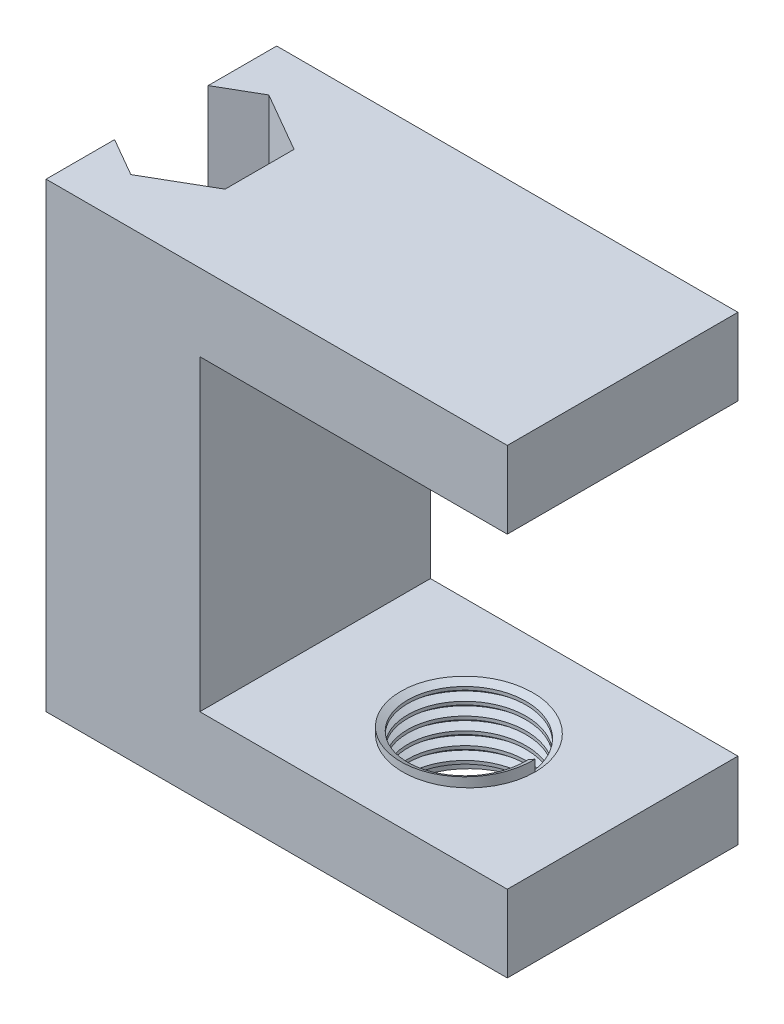
SolidWorks part; units mm, degrees
ref_plane "Front Plane" through (0, 0, 0) normal (0, 0, 1) x (1, 0, 0)
ref_plane "Top Plane" through (0, 0, 0) normal (0, 1, 0) x (1, 0, 0)
ref_plane "Right Plane" through (0, 0, 0) normal (1, 0, 0) x (0, 0, -1)
sketch "Sketch1" plane through (0, 0, 0) normal (0, 0, 1) x (1, 0, 0)
  line L1 (-19.05, -19.05) -> (19.05, -19.05)
  line L2 (-19.05, -19.05) -> (-19.05, 19.05)
  line L3 (-19.05, 19.05) -> (19.05, 19.05)
  line L4 (19.05, -19.05) -> (19.05, 19.05)
  line L5 (-19.05, -19.05) -> (19.05, 19.05) construction
  line L6 (-19.05, 19.05) -> (19.05, -19.05) construction
  point P0 (0, 0)
  dimension "D1" = 38.1
  dimension "D2" = 38.1
extrude "Boss-Extrude1" add sketch "Sketch1" against normal blind 19.05
sketch "Sketch2" plane through (0, 0, 0) normal (0, 0, 1) x (1, 0, 0)
  line L0 (19.05, 12.7) -> (-6.35, 12.7)
  line L1 (19.05, -19.05) -> (19.05, 19.05) construction
  line L2 (-6.35, 12.7) -> (-6.35, -12.7)
  line L3 (-6.35, -12.7) -> (19.05, -12.7)
  line L4 (19.05, -12.7) -> (19.05, 12.7)
  line L5 (19.05, 19.05) -> (-19.05, 19.05) construction
  line L6 (-19.05, -19.05) -> (19.05, -19.05) construction
  line L7 (-19.05, 19.05) -> (-19.05, -19.05) construction
  dimension "D1" = 6.35
  dimension "D2" = 6.35
  dimension "D3" = 12.7
extrude "Cut-Extrude1" cut sketch "Sketch2" against normal up to next
sketch "Sketch3" plane through (0, 19.05, 0) normal (0, 1, 0) x (1, 0, 0)
  line L0 (-19.05, 9.525) -> (19.05, 9.525) construction
  line L1 (-19.05, 19.05) -> (-19.05, 0) construction
  line L2 (19.05, 19.05) -> (19.05, 0) construction
  line L4 (-12.7, 11.3581) -> (-15.875, 13.1912)
  line L5 (-15.875, 13.1912) -> (-19.05, 11.3581)
  line L6 (-19.05, 11.3581) -> (-19.05, 7.6919)
  line L7 (-19.05, 7.6919) -> (-15.875, 5.8588)
  line L8 (-15.875, 5.8588) -> (-12.7, 7.6919)
  line L9 (-12.7, 7.6919) -> (-12.7, 11.3581)
  circle A0 centre (-15.875, 9.525) radius 3.175 construction
  dimension "D1" = 6.35
extrude "Cut-Extrude2" cut sketch "Sketch3" against normal up to next
sketch "Sketch4" plane through (0, 19.05, 0) normal (0, 1, 0) x (1, 0, 0)
  line L0 (19.05, 9.525) -> (-19.05, 9.525) construction
  line L1 (19.05, 19.05) -> (19.05, 0) construction
  line L2 (-15.875, 13.7201) -> (-15.875, 24.6297) construction
  line L3 (-19.05, 7.6919) -> (-6.001, 15.2258) construction
  line L4 (-19.05, 11.3581) -> (-13.6473, 8.2388) construction
  line L5 (-19.05, 13.3901) -> (-15.875, 15.2232)
  line L6 (-19.05, 19.05) -> (-19.05, 11.3581) construction
  line L7 (-15.875, 15.2232) -> (-10.9402, 12.3741)
  line L8 (-10.9402, 12.3741) -> (-10.9402, 6.6759)
  line L9 (-10.9402, 6.6759) -> (-15.875, 3.8268)
  line L10 (-15.875, 3.8268) -> (-19.05, 5.6599)
  line L11 (-19.05, 7.6919) -> (-19.05, 0) construction
  line L12 (-19.05, 5.6599) -> (-19.05, 7.6919)
  line L13 (-19.05, 13.3901) -> (-19.05, 11.3581)
  line L14 (-19.05, 11.3581) -> (-15.875, 13.1912)
  line L15 (-15.875, 13.1912) -> (-12.7, 11.3581)
  line L16 (-12.7, 11.3581) -> (-12.7, 7.6919)
  line L17 (-12.7, 7.6919) -> (-15.875, 5.8588)
  line L18 (-15.875, 5.8588) -> (-19.05, 7.6919)
  dimension "D1" = 2.032
  dimension "D2" = 2.032
  dimension "D3" = 2.032
  dimension "D4" = 2.032
  dimension "D5" = 2.032
extrude "Cut-Extrude3" cut sketch "Sketch4" against normal blind 31.75
sketch "Sketch5" plane through (0, -19.05, 0) normal (0, -1, 0) x (1, 0, 0)
  line L0 (19.05, -9.525) -> (-19.3242, -9.525) construction
  line L1 (19.05, -19.05) -> (19.05, 0) construction
  line L2 (19.05, 0) -> (-6.35, 0) construction
  line L3 (-19.05, 0) -> (19.05, 0) construction
  line L4 (-6.35, 0) -> (-6.35, -9.525) construction
  line L5 (6.35, 0) -> (6.35, -9.525) construction
  circle A0 centre (6.35, -9.525) radius 5.461
  dimension "D2" = 10.922
  dimension "D1" = 25.4
extrude "Cut-Extrude4" cut sketch "Sketch5" against normal up to next
thread "Thread1" pitch 1.0583 method extrude profile "Thread Profile1" start angle 0, offset 0, length 0, pitch 1.0583, diameter 10.922
ref_plane "Plane1" through (11.811, -19.05, -9.525) normal (0, 0, 1) x (1, 0, 0)
sketch "Thread Profile1" plane through (11.811, -19.05, -9.525) normal (0, 0, 1) x (1, 0, 0)
  line L0 (0, 0) -> (0, 1.0583) construction
  line L11 (0, 0) -> (0, 0.926)
  line L12 (0, 0.926) -> (-0.5728, 0.5953)
  line L13 (-0.5728, 0.5953) -> (-0.5728, 0.3307)
  line L15 (-0.5728, 0.3307) -> (0, 0)
  line L17 (-0.5728, 0.463) -> (0, 0.463) construction
  point P2 (0, 0)
  dimension "Pitch" = 1.0583
  dimension "Profile_Angle" = 60
  dimension "Profile_Land" = 0.2646
  dimension "Profile_Height" = 0.5728
equation "\"G\"= 0.08"
equation "\"D1@Sketch4\"=\"G\""
equation "\"D2@Sketch4\"=\"G\""
equation "\"D3@Sketch4\"=\"G\""
equation "\"D4@Sketch4\"=\"G\""
equation "\"D5@Sketch4\"=\"G\""
